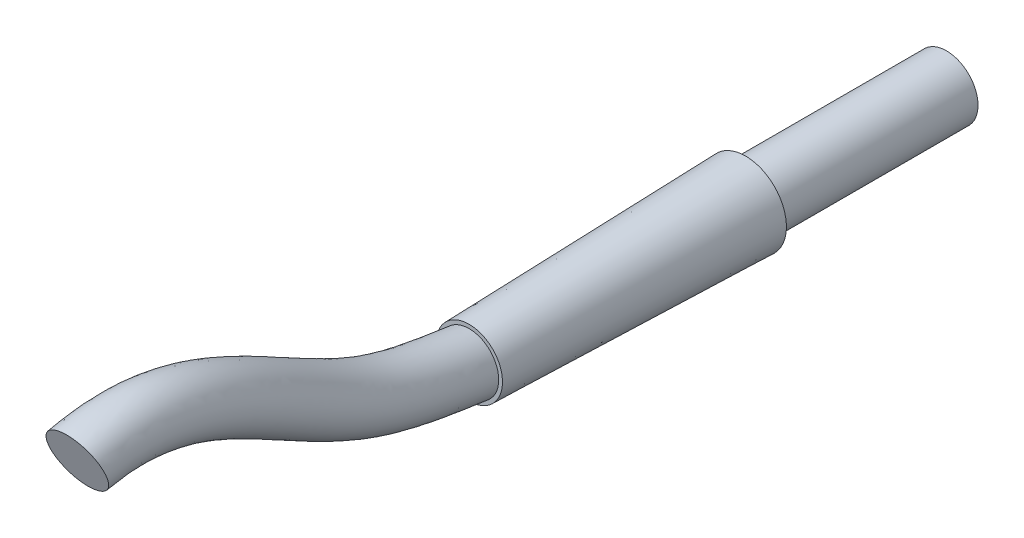
SolidWorks part; units mm, degrees
ref_plane "前视基准面" through (0, 0, 0) normal (0, 0, 1) x (1, 0, 0)
ref_plane "上视基准面" through (0, 0, 0) normal (0, 1, 0) x (1, 0, 0)
ref_plane "右视基准面" through (0, 0, 0) normal (1, 0, 0) x (0, 0, -1)
sketch "草图1" plane through (0, 0, 0) normal (0, 0, 1) x (1, 0, 0)
  circle A0 centre (0, 0) radius 2.5
  circle A1 centre (0, 0) radius 1.3
  dimension "D1" = 5
  dimension "D2" = 2.6
extrude "凸台-拉伸1" add sketch "草图1" along normal blind 16
cosmetic thread "装饰螺纹线1" parameters "D2"=4.134
sketch "草图3" plane through (0, 0, 0) normal (0, 1, 0) x (1, 0, 0)
  line L0 (0, -15.7733) -> (0, -30.1802) construction
  line L1 (-3.25, -16) -> (0, -16)
  line L2 (-2.5, -16) -> (2.5, -16) construction
  line L3 (-3.25, -16) -> (-2.65, -38)
  line L4 (-2.65, -38) -> (0, -38)
  line L5 (0, -16) -> (0, -38)
  dimension "D1" = 3.25
  dimension "D2" = 2.65
  dimension "D3" = 22
revolve "旋转1" add sketch "草图3" angle 360 about L0
sketch "草图4" plane through (0, 0, 0) normal (1, 0, 0) x (0, 0, -1)
  line L0 (-38, 2.65) -> (-38, -2.65) construction
  spline S0 degree 3 poles (-38, 0) (-40.6217, 0.3829) (-51.5209, 2.0228) (-59.7667, 10.999) (-69.1895, 8.8509) knots 0 0 0 0 0.245937 1 1 1 1
sketch "草图5" plane through (0, 0, 38) normal (0, 0, 1) x (1, 0, 0)
  circle A0 centre (0, 0) radius 2.35
  dimension "D1" = 4.7
sweep "扫描2" add profiles "草图5" path "草图4"
